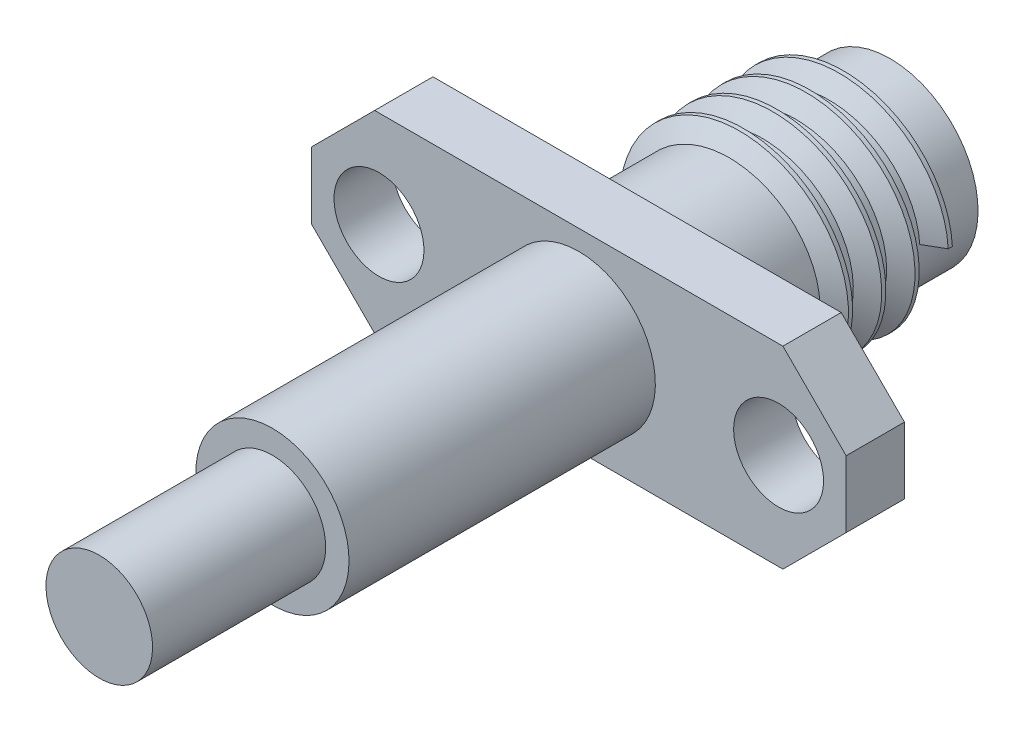
SolidWorks part; units mm, degrees
ref_plane "Front Plane" through (0, 0, 0) normal (0, 0, 1) x (1, 0, 0)
ref_plane "Top Plane" through (0, 0, 0) normal (0, 1, 0) x (1, 0, 0)
ref_plane "Right Plane" through (0, 0, 0) normal (1, 0, 0) x (0, 0, -1)
sketch "Sketch5" plane through (0.2127, -0.1613, 0) normal (0, 0, -1) x (-1, 0, 0)
  circle A0 centre (0.2127, 0.1613) radius 1.6
  dimension "D1" = 3.2
extrude "Antenna connector wire start" add sketch "Sketch5" along normal blind 5.2
sketch "Sketch6" plane through (0, 0, -5.2) normal (0, 0, -1) x (-1, 0, 0)
  circle A0 centre (0, 0) radius 2.3
  dimension "D1" = 4.6
extrude "Antenna connector wire end" add sketch "Sketch6" along normal blind 9.2
sketch "Sketch7" plane through (0, 0, -14.4) normal (0, 0, -1) x (-1, 0, 0)
  line L0 (-8.03, 0) -> (8.03, 0) construction
  line L1 (8.03, -2.9) -> (-8.03, -2.9)
  line L2 (8.03, -2.9) -> (8.03, 2.9)
  line L3 (8.03, 2.9) -> (-8.03, 2.9)
  line L4 (-8.03, -2.9) -> (-8.03, 2.9)
  line L5 (8.03, -2.9) -> (-8.03, 2.9) construction
  line L6 (8.03, 2.9) -> (-8.03, -2.9) construction
  line L7 (0, 2.9) -> (0, -2.9) construction
  line L8 (-8.03, 1) -> (-6.13, 2.9)
  line L9 (8.03, 1) -> (6.13, 2.9)
  line L10 (8.03, -1) -> (6.13, -2.9)
  line L11 (-8.03, -1) -> (-6.13, -2.9)
  circle A0 centre (-6, 0) radius 1.35
  circle A1 centre (6, 0) radius 1.35
  point P0 (0, 0)
  circle M8 centre (0, 0) radius 2.3
  dimension "D3" = 2.7
  dimension "D1" = 5.8
  dimension "D2" = 16.06
  dimension "D4" = 12
  dimension "D5" = 45
  dimension "D6" = 2
extrude "Antenna connector mount" add sketch "Sketch7" along normal blind 1.75 contours L4 L11 L1 L10 L2 L9 L3 L8 A0 A1 M8 | M8 region at (0, -2.7292, -14.4) region at (0, 0, -14.4)
sketch "Sketch8" plane through (0, 0, -16.15) normal (0, 0, -1) x (-1, 0, 0)
  line L0 (-8.03, 0) -> (8.03, 0) construction
  line L1 (-8.03, -1) -> (-8.03, 1) construction
  line L2 (8.03, -1) -> (8.03, 1) construction
  line L3 (0, 2.9) -> (0, -2.9) construction
  line L4 (6.13, 2.9) -> (-6.13, 2.9) construction
  line L5 (6.13, -2.9) -> (-6.13, -2.9) construction
  circle A0 centre (0, 0) radius 2.64
  dimension "D1" = 5.28
extrude "Antenna connector shaft" add sketch "Sketch8" along normal blind 2.7
sketch "Sketch9" plane through (0, 0, -18.85) normal (0, 0, -1) x (-1, 0, 0)
  circle A0 centre (0, 0) radius 2.64
  circle A1 centre (0, 0) radius 2.64 construction
extrude "Antenna connector middle" add sketch "Sketch9" along normal blind 3.9
sketch "Sketch10" plane through (0, 0, -22.75) normal (0, 0, -1) x (-1, 0, 0)
  circle A0 centre (0, 0) radius 2.64
  circle A1 centre (0, 0) radius 2.64 construction
extrude "Antenna connector tip" add sketch "Sketch10" along normal blind 1
sketch "Sketch11" plane through (0, 0, -23.75) normal (0, 0, -1) x (-1, 0, 0)
  circle A0 centre (0, 0) radius 2.35
  dimension "D1" = 4.7
extrude "Antenna connector hole" cut sketch "Sketch11" against normal blind 1.9
sketch "Sketch12" plane through (0, 0, -21.85) normal (0, 0, -1) x (-1, 0, 0)
  circle A0 centre (0, 0) radius 0.5
  dimension "D1" = 1
extrude "Antenna connector mate" cut sketch "Sketch12" against normal blind 2.5
thread "Antenna connector thread" pitch 1 method extrude profile "Thread Profile1" start angle 0, offset 1, length 4, pitch 1, diameter 5.28
ref_plane "Plane1" through (2.64, 0, -22.75) normal (0, -1, 0) x (1, 0, 0)
sketch "Thread Profile1" plane through (2.64, 0, -22.75) normal (0, -1, 0) x (1, 0, 0)
  line L0 (0, 0) -> (0, 1) construction
  line L1 (0, 0) -> (0.5413, 0.3125)
  line L2 (0.5413, 0.3125) -> (0.5413, 0.4375)
  line L3 (0.5413, 0.4375) -> (0, 0.75)
  line L4 (0.5413, 0.375) -> (0, 0.375) construction
  line L11 (0, 0) -> (0, 0.75)
  point P2 (0, 0)
  dimension "Pitch" = 1
  dimension "Profile_Angle" = 60
  dimension "Profile_Land" = 0.125
  dimension "Profile_Height" = 0.5413
